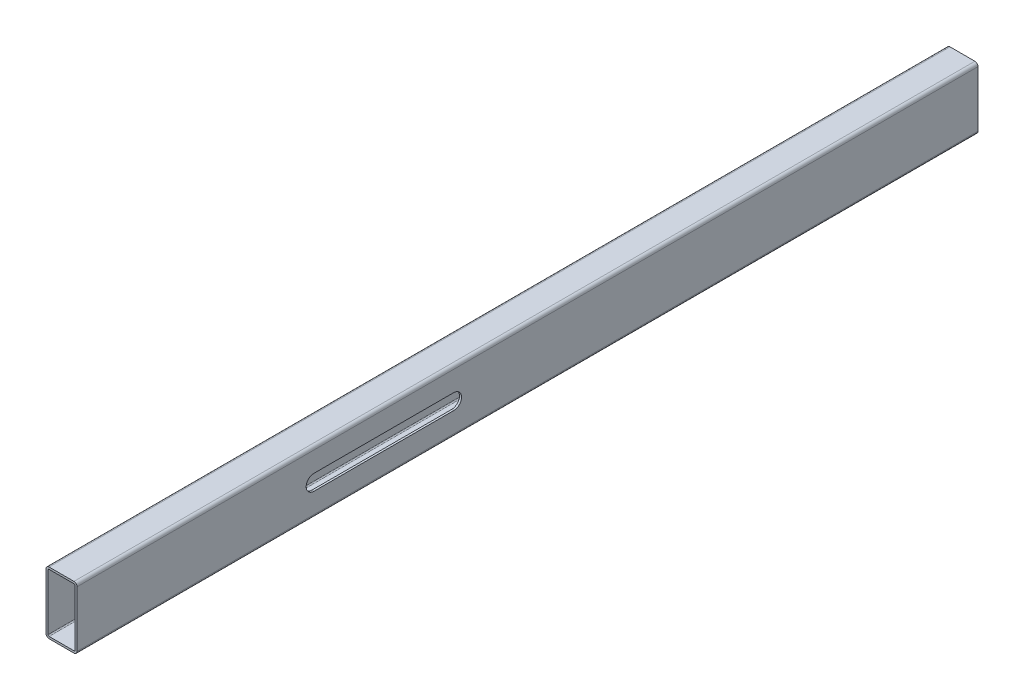
SolidWorks part; units mm, degrees
material "6061-T6 (SS)"
ref_plane "Front Plane" through (0, 0, 0) normal (0, 0, 1) x (1, 0, 0)
ref_plane "Top Plane" through (0, 0, 0) normal (0, 1, 0) x (1, 0, 0)
ref_plane "Right Plane" through (0, 0, 0) normal (1, 0, 0) x (0, 0, -1)
sketch "Sketch1" plane through (0, 0, 0) normal (0, 0, 1) x (1, 0, 0)
  line L1 (10.16, -25.4) -> (-10.16, -25.4)
  line L2 (12.7, -22.86) -> (12.7, 22.86)
  line L3 (10.16, 25.4) -> (-10.16, 25.4)
  line L4 (-12.7, -22.86) -> (-12.7, 22.86)
  line L5 (12.7, -25.4) -> (-12.7, 25.4) construction
  line L6 (12.7, 25.4) -> (-12.7, -25.4) construction
  arc A0 (-10.16, -25.4) -> (-12.7, -22.86) centre (-10.16, -22.86) cw
  arc A1 (10.16, -25.4) -> (12.7, -22.86) centre (10.16, -22.86) ccw
  arc A2 (12.7, 22.86) -> (10.16, 25.4) centre (10.16, 22.86) ccw
  arc A3 (-10.16, 25.4) -> (-12.7, 22.86) centre (-10.16, 22.86) ccw
  point P0 (0, 0)
  dimension "D3" = 2.54
  dimension "D1" = 25.4
  dimension "D2" = 50.8
extrude "Extrude-Thin1" add sketch "Sketch1" along normal blind 736.6 thin thin type one direction reverse wall 1.651
sketch "Sketch2" [suppressed] plane through (-12.7, 0, 0) normal (-1, 0, 0) x (0, 0, 1)
  line L0 (25.4, 0) -> (152.4, 0) construction
  line L1 (25.4, 6.35) -> (152.4, 6.35)
  line L2 (25.4, -6.35) -> (152.4, -6.35)
  line L3 (0, 22.86) -> (0, -22.86) construction
  arc A0 (25.4, 6.35) -> (25.4, -6.35) centre (25.4, 0) ccw
  arc A1 (152.4, -6.35) -> (152.4, 6.35) centre (152.4, 0) ccw
  point P3 (88.9, 0)
  dimension "D1" = 12.7
  dimension "D2" = 127
  dimension "D3" = 25.4
extrude "Cut-Extrude1" [suppressed] cut sketch "Sketch2" against normal through all
sketch "Sketch3" plane through (-12.7, 0, 0) normal (-1, 0, 0) x (0, 0, 1)
  line L0 (542.925, 0) -> (428.625, 0) construction
  line L1 (542.925, -6.35) -> (428.625, -6.35)
  line L2 (542.925, 6.35) -> (428.625, 6.35)
  line L3 (736.6, 22.86) -> (736.6, -22.86) construction
  arc A0 (542.925, -6.35) -> (542.925, 6.35) centre (542.925, 0) ccw
  arc A1 (428.625, 6.35) -> (428.625, -6.35) centre (428.625, 0) ccw
  point P3 (485.775, 0)
  dimension "D1" = 12.7
  dimension "D2" = 193.675
  dimension "D3" = 114.3
extrude "Cut-Extrude2" cut sketch "Sketch3" against normal through all
